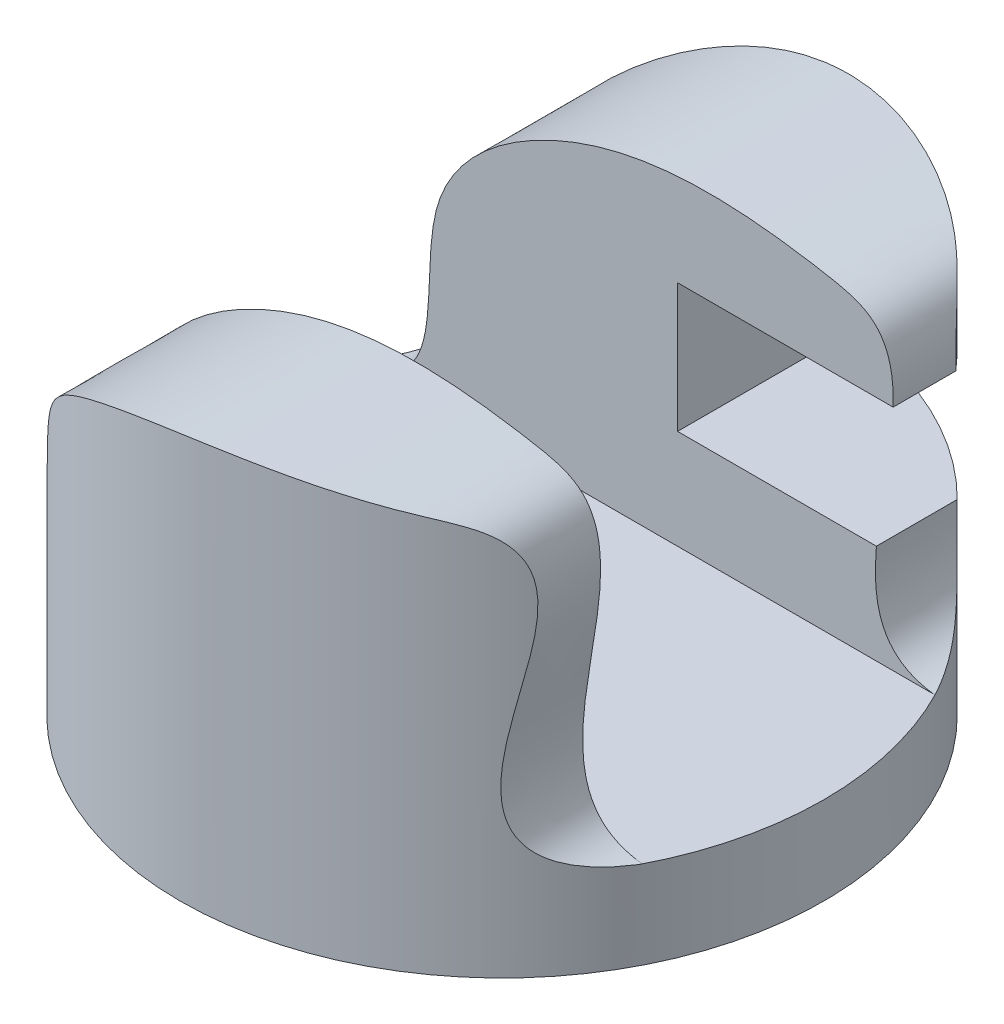
SolidWorks part; units mm, degrees
ref_plane "Front Plane" through (0, 0, 0) normal (0, 0, 1) x (1, 0, 0)
ref_plane "Top Plane" through (0, 0, 0) normal (0, 1, 0) x (1, 0, 0)
ref_plane "Right Plane" through (0, 0, 0) normal (1, 0, 0) x (0, 0, -1)
sketch "Sketch1" plane through (0, 0, 0) normal (0, 1, 0) x (1, 0, 0)
  circle A0 centre (0, 0) radius 55
  dimension "D1" = 110
extrude "Boss-Extrude1" add sketch "Sketch1" along normal blind 80
sketch "Sketch5" plane through (0, 0, 0) normal (0, 1, 0) x (1, 0, 0)
  line L1 (55.3407, -25) -> (-55.3407, -25)
  line L2 (55.3407, -25) -> (55.3407, 25)
  line L3 (55.3407, 25) -> (-55.3407, 25)
  line L4 (-55.3407, -25) -> (-55.3407, 25)
  line L5 (55.3407, -25) -> (-55.3407, 25) construction
  line L6 (55.3407, 25) -> (-55.3407, -25) construction
  point P0 (0, 0)
  dimension "D1" = 50
extrude "Cut-Extrude2" cut sketch "Sketch5" along normal blind 85 from offset 15
sketch "Sketch4" plane through (0, 0, 0) normal (0, 0, 1) x (1, 0, 0)
  line L0 (-55, 15) -> (55, 15)
  line L5 (-55, 0) -> (55, 0) construction
  line L6 (55, 80) -> (-55, 80) construction
  line L7 (-55, 15) -> (-94.8282, 60.4525)
  line L8 (-94.8282, 60.4525) -> (-52.2656, 84.774)
  line L9 (-52.2656, 84.774) -> (65.61, 86.1787)
  line L10 (65.61, 86.1787) -> (71.585, 38.1442)
  line L11 (71.585, 38.1442) -> (55, 15)
  line L15 (-55, 15) -> (-55, 0) construction
  line L16 (-55, 15) -> (-55, 0)
  line L17 (55, 0) -> (55, 15) construction
  line L18 (55, 0) -> (55, 15)
  line L19 (48.9898, 80) -> (48.9898, 15) construction
  line L20 (-48.9898, 15) -> (-48.9898, 80) construction
  spline S0 degree 3 poles (-55, 15) (-31.7624, 13.3309) (-45.7599, 45.0444) (-10.2587, 71.3903) (16.6588, 70.7317) (56.6638, 62.711) (21.5379, 11.6598) (55, 15) knots 0 0 0 0 0.221887 0.380112 0.626066 0.665786 1 1 1 1
  point P2 (-35.9898, 45)
  point P9 (-38.9898, 22)
  point P10 (-14.9898, 65)
  point P11 (29.9898, 68)
  dimension "D1" = 15
  dimension "D2" = 15
  dimension "D3" = 7
  dimension "D4" = 12
  dimension "D5" = 30
  dimension "D6" = 19
  dimension "D7" = 50
  dimension "D8" = 12
  dimension "D9" = 34
  dimension "D10" = 14
  dimension "D11" = 13
  dimension "D12" = 10
  dimension "D14" = 6
extrude "Cut-Extrude1" cut sketch "Sketch4" against normal through all both and the other way through all contours L7 S0 L11 L10 L9 L8 region at (-73.5528, 38.9191, 0)
sketch "Sketch6" plane through (0, 0, 25) normal (0, 0, -1) x (-1, 0, 0)
  line L0 (48.9898, 15) -> (-48.8004, 15) construction
  circle A0 centre (-18, 43) radius 11.2
  dimension "D1" = 22.4
  dimension "D2" = 18
  dimension "D3" = 28
extrude "Cut-Extrude3" cut sketch "Sketch6" against normal blind 8
sketch "Sketch7" plane through (0, 0, -25) normal (0, 0, 1) x (1, 0, 0)
  line L0 (48.8004, 15) -> (-48.9898, 15) construction
  line L1 (46.2118, 32) -> (5, 32)
  line L2 (46.2118, 32) -> (46.2118, 54)
  line L3 (46.2118, 54) -> (5, 54)
  line L4 (5, 32) -> (5, 54)
  line L5 (46.2118, 32) -> (5, 54) construction
  line L6 (46.2118, 54) -> (5, 32) construction
  point P0 (25.6059, 43)
  point P5 (18, 43)
  dimension "D1" = 13
  dimension "D2" = 18
  dimension "D3" = 28
  dimension "D4" = 22
extrude "Cut-Extrude4" cut sketch "Sketch7" against normal blind 48
